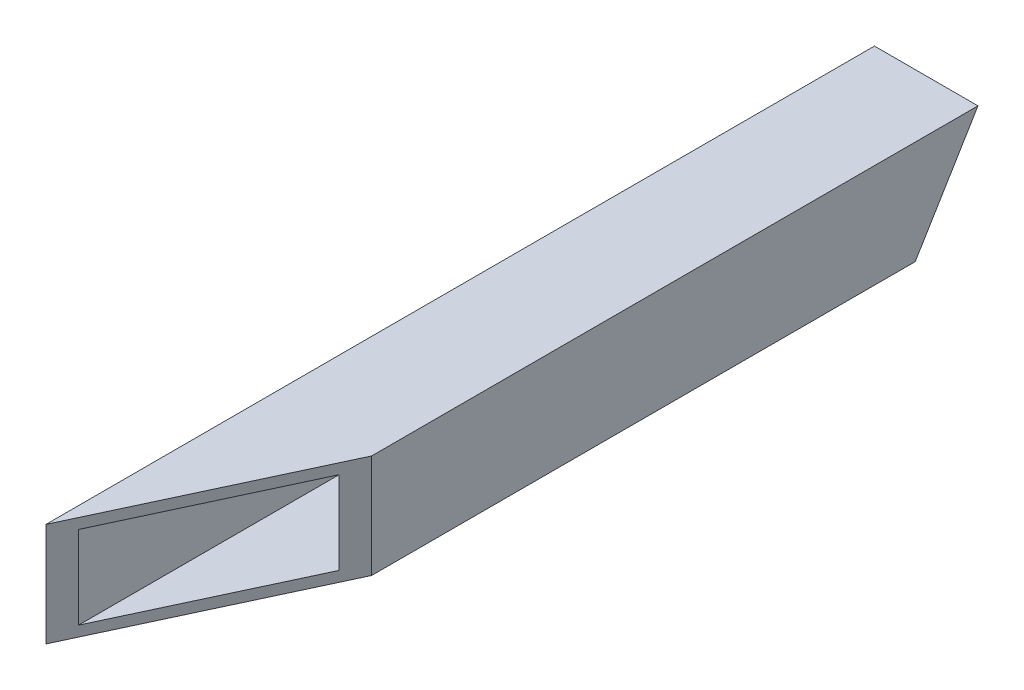
SolidWorks part; units mm, degrees
ref_plane "Front Plane" through (0, 0, 0) normal (0, 0, 1) x (1, 0, 0)
ref_plane "Top Plane" through (0, 0, 0) normal (0, 1, 0) x (1, 0, 0)
ref_plane "Right Plane" through (0, 0, 0) normal (1, 0, 0) x (0, 0, -1)
sketch "Sketch1" plane through (0, 0, 0) normal (0, 0, 1) x (1, 0, 0)
  line L0 (-10.16, 10.16) -> (10.16, 10.16)
  line L1 (-12.7, -12.7) -> (12.7, -12.7)
  line L2 (-12.7, -12.7) -> (-12.7, 12.7)
  line L3 (-12.7, 12.7) -> (12.7, 12.7)
  line L4 (12.7, -12.7) -> (12.7, 12.7)
  line L5 (-12.7, -12.7) -> (12.7, 12.7) construction
  line L6 (-12.7, 12.7) -> (12.7, -12.7) construction
  line L7 (10.16, -10.16) -> (10.16, 10.16)
  line L8 (-10.16, -10.16) -> (10.16, -10.16)
  line L9 (-10.16, -10.16) -> (-10.16, 10.16)
  point P0 (0, 0)
  dimension "D1" = 25.4
  dimension "D2" = 25.4
  dimension "D3" = 2.54
extrude "Boss-Extrude2" add sketch "Sketch1" along normal blind 203.2
sketch "Sketch2" plane through (0, 12.7, 0) normal (0, 1, 0) x (1, 0, 0)
  line L0 (-12.7, -203.2) -> (12.7, -148.7295)
  line L1 (12.7, -203.2) -> (12.7, 0) construction
  line L2 (12.7, -148.7295) -> (12.7, -203.2)
  line L3 (12.7, -203.2) -> (-12.7, -203.2)
  line L4 (-12.7, -101.6) -> (12.7, -101.6) construction
  line L5 (-12.7, -203.2) -> (-12.7, 0) construction
  dimension "D1" = 65
extrude "Cut-Extrude1" cut sketch "Sketch2" against normal through all
sketch "Sketch3" plane through (12.7, 0, 0) normal (1, 0, 0) x (0, 0, -1)
  line L1 (-148.7295, 0) -> (0, 0) construction
  line L3 (0, -12.7) -> (0, 12.7)
  line L5 (-148.7295, -12.7) -> (-148.7295, 12.7) construction
  line L6 (-15.3913, 12.7) -> (0, -12.7)
  line L7 (0, 12.7) -> (-15.3913, 12.7)
  dimension "D1" = 31.214
extrude "Cut-Extrude2" [suppressed] cut sketch "Sketch3" against normal through all
sketch "Sketch4" plane through (12.7, 0, 0) normal (1, 0, 0) x (0, 0, -1)
  line L0 (0, 12.7) -> (-15.3913, -12.7)
  line L1 (-148.7295, -12.7) -> (0, -12.7) construction
  line L2 (-15.3913, -12.7) -> (0, -12.7)
  line L3 (0, -12.7) -> (0, 12.7)
  dimension "D1" = 31.214
extrude "Cut-Extrude3" cut sketch "Sketch4" against normal through all
